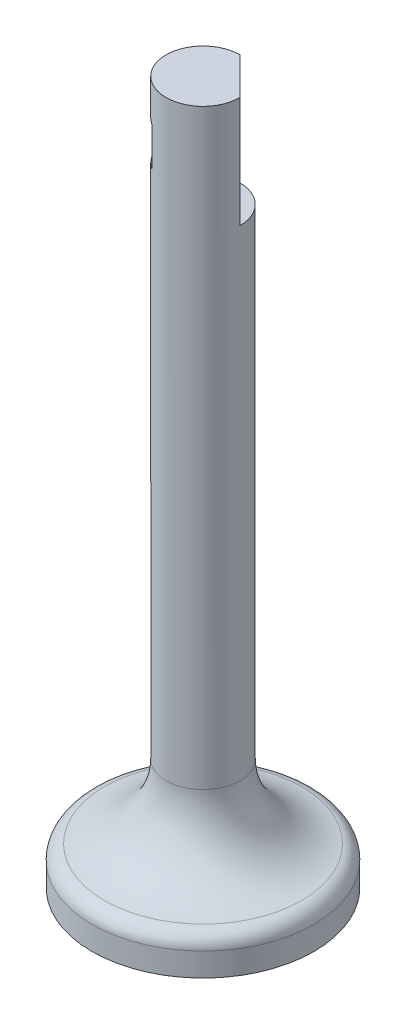
SolidWorks part; units mm, degrees
ref_plane "Спереди" through (0, 0, 0) normal (0, 0, 1) x (1, 0, 0)
ref_plane "Сверху" through (0, 0, 0) normal (0, 1, 0) x (1, 0, 0)
ref_plane "Справа" through (0, 0, 0) normal (1, 0, 0) x (0, 0, -1)
sketch "Sketch1" plane through (0, 0, 0) normal (0, 1, 0) x (1, 0, 0)
  circle A0 centre (0, 0) radius 15
  dimension "D1" = 30
extrude "Boss-Extrude1" add sketch "Sketch1" along normal blind 5
sketch "Sketch2" plane through (0, 5, 0) normal (0, 1, 0) x (1, 0, 0)
  circle A0 centre (0, 0) radius 5
  dimension "D1" = 10
extrude "Boss-Extrude2" add sketch "Sketch2" along normal blind 90
sketch "Sketch3" plane through (0, 95, 0) normal (0, 1, 0) x (1, 0, 0)
  line L0 (0, 5) -> (5, 0)
  circle A0 centre (0, 0) radius 5 construction
  arc A1 (0, 5) -> (5, 0) centre (0, 0) cw
extrude "Cut-Extrude1" cut sketch "Sketch3" against normal blind 15
sketch "Sketch4" plane through (2.5, 0, -2.5) normal (0.7071, 0, -0.7071) x (-0.7071, 0, -0.7071)
  line L0 (0, 95) -> (0, 80) construction
  line L1 (3.5355, 95) -> (-3.5355, 95) construction
  line L2 (3.5355, 80) -> (-3.5355, 80) construction
  line L4 (1, 90.1) -> (-1, 90.1)
  line L5 (1, 90.1) -> (1, 84.9)
  line L6 (1, 84.9) -> (-1, 84.9)
  line L7 (-1, 90.1) -> (-1, 84.9)
  line L8 (1, 90.1) -> (-1, 84.9) construction
  line L9 (1, 84.9) -> (-1, 90.1) construction
  point P6 (0, 87.5)
  dimension "D1" = 5.2
  dimension "D2" = 2
extrude "Cut-Extrude2" cut sketch "Sketch4" against normal through all
fillet "Fillet1" radius 10 1 edges at (0, 5, 5)
fillet "Fillet2" radius 2 1 edges at (0, 5, 15)
sketch "Sketch5" plane through (0, 0, 0) normal (0, -1, 0) x (1, 0, 0)
  line L0 (10.6066, -10.6066) -> (-10.6066, 10.6066) construction
  line L1 (3.3153, 14.629) -> (-14.629, -3.3153) construction
  line L2 (0, -5) -> (5, 0) construction
  circle A0 centre (0, 0) radius 15 construction
  text T0 "P" font "Arial" height 16
  point P2 (-5.6569, 5.6569)
  dimension "D1" = 7
extrude "Cut-Extrude3" cut sketch "Sketch5" against normal blind 1
sketch "Sketch6" plane through (0, 0, 0) normal (0, -1, 0) x (1, 0, 0)
  circle A0 centre (0, 0) radius 11.5
  circle A1 centre (0, 0) radius 13.5
  dimension "D1" = 2
  dimension "D2" = 27
extrude "Cut-Extrude4" cut sketch "Sketch6" against normal blind 1
